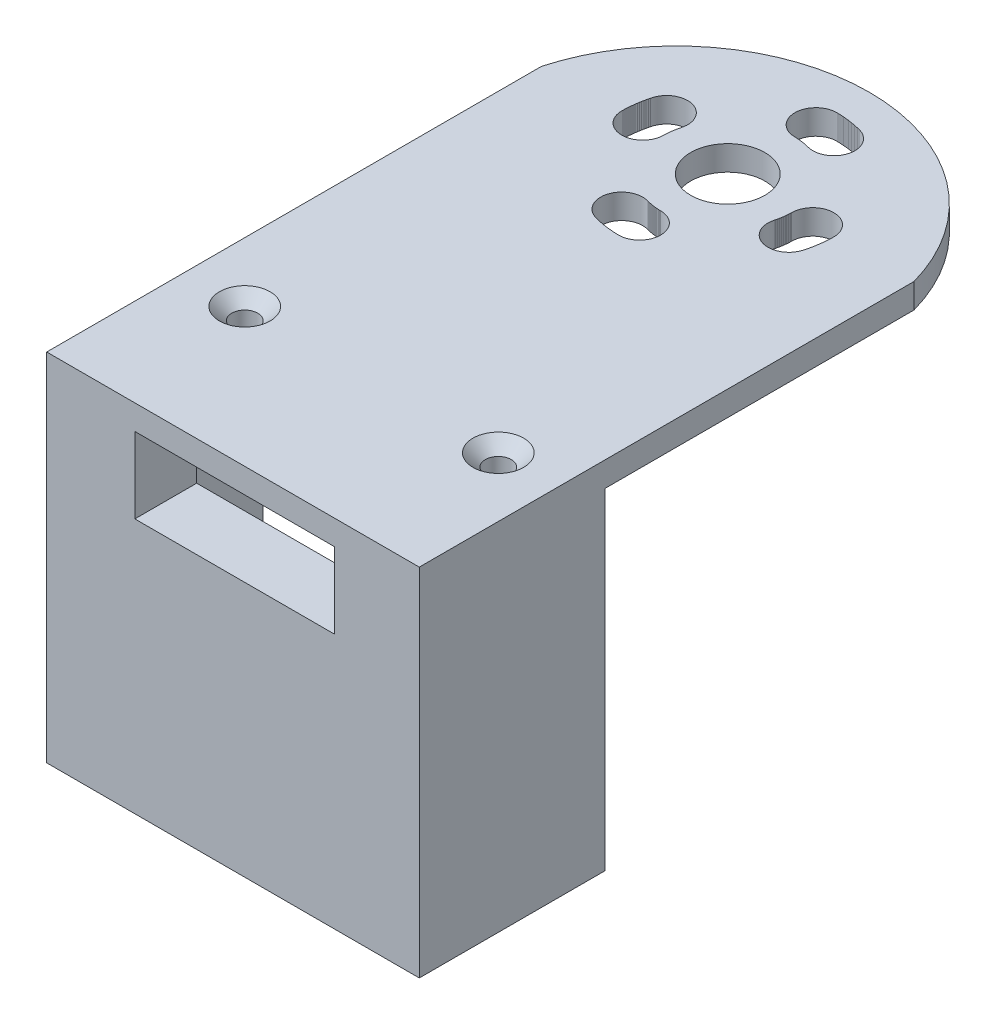
SolidWorks part; units mm, degrees
ref_plane "Front Plane" through (0, 0, 0) normal (0, 0, 1) x (1, 0, 0)
ref_plane "Top Plane" through (0, 0, 0) normal (0, 1, 0) x (1, 0, 0)
ref_plane "Right Plane" through (0, 0, 0) normal (1, 0, 0) x (0, 0, -1)
sketch "Sketch2" plane through (0, 0, 0) normal (0, 1, 0) x (1, 0, 0)
  line L0 (15.061, 0) -> (15.061, 32)
  line L1 (-12.561, 2.5) -> (12.561, 2.5)
  line L2 (-12.561, 2.5) -> (-12.561, 32)
  line L4 (12.561, 2.5) -> (12.561, 32)
  line L5 (15.061, 32) -> (12.561, 32)
  line L7 (-15.061, 32) -> (-15.061, 0)
  line L8 (-15.061, 0) -> (15.061, 0)
  line L10 (-15.061, 32) -> (-12.561, 32)
  point P4 (0, 2.5)
  point P12 (0, 0)
  dimension "D1" = 2.5
  dimension "D2" = 2.5
  dimension "D3" = 29.5
  dimension "D4" = 25.122
extrude "Boss-Extrude1" add sketch "Sketch2" along normal blind 32.5
sketch "Sketch4" plane through (0, 0, 0) normal (0, -1, 0) x (1, 0, 0)
  line L10 (-7.561, -6) -> (-7.561, 0)
  line L13 (-12.561, -2.5) -> (-12.561, -32) construction
  line L18 (-12.561, -10) -> (-7.561, -6)
  line L23 (12.561, -32) -> (12.561, -2.5) construction
  line L26 (12.561, -10) -> (7.561, -6)
  line L33 (-15.061, -32) -> (-15.061, 0) construction
  line L36 (15.061, 0) -> (15.061, -32) construction
  line L38 (-7.561, 0) -> (-15.061, 0)
  line L39 (7.561, -6) -> (7.561, 0)
  line L40 (7.561, 0) -> (15.061, 0)
  line L41 (-15.061, 0) -> (-15.061, -32)
  line L42 (-15.061, -32) -> (-12.561, -32)
  line L43 (-12.561, -32) -> (-15.061, -32) construction
  line L44 (-12.561, -32) -> (-12.561, -10)
  line L45 (12.561, -10) -> (12.561, -32)
  line L46 (12.561, -32) -> (15.061, -32)
  line L47 (15.061, -32) -> (15.061, 0)
  circle A2 centre (-10.2499, -4.95) radius 1.05
  circle A5 centre (10.2499, -4.95) radius 1.05
  dimension "D4" = 6
  dimension "D5" = 2.1
  dimension "D1" = 7.5
  dimension "D2" = 7.5
  dimension "D3" = 10
extrude "Boss-Extrude2" add sketch "Sketch4" along normal blind 2.5
sketch "Sketch5" plane through (0, 32.5, 0) normal (0, 1, 0) x (1, 0, 0)
  line L0 (-15.061, 32) -> (-10.2499, 32)
  line L9 (-10.2499, 32) -> (-6.25, 26)
  line L13 (-15.061, 0) -> (15.061, 0) construction
  line L14 (15.061, 0) -> (-15.061, 0)
  line L15 (-15.061, 0) -> (-15.061, 32)
  line L20 (15.061, 0) -> (15.061, 32)
  line L21 (-6.25, 26) -> (6.25, 26)
  line L22 (6.25, 26) -> (10.2499, 32)
  line L23 (10.2499, 32) -> (15.061, 32)
  circle A0 centre (-10.2499, 4.95) radius 1.05 construction
  circle A1 centre (-10.2499, 8.7) radius 1.05
  circle A2 centre (10.2499, 8.7) radius 1.05
  point P6 (0, 26)
  dimension "D4" = 0
  dimension "D1" = 8.7
  dimension "D2" = 12.5
  dimension "D3" = 20.4998
  dimension "D5" = 6
extrude "Boss-Extrude3" add sketch "Sketch5" along normal blind 3
sketch "Sketch6" plane through (-15.061, 0, 0) normal (-1, 0, 0) x (0, 0, 1)
  line L1 (-32, -2.5) -> (-32, 29.6998)
  line L5 (-32, 35.5) -> (-32, -2.5) construction
  line L7 (0, 35.5) -> (0, -2.5) construction
  line L8 (-12.5, -2.5) -> (-12.5, 35.5)
  line L9 (-32, 35.5) -> (0, 35.5) construction
  line L10 (-12.5, 35.5) -> (-32, 35.5)
  line L11 (-32, 35.5) -> (-32, 29.6998)
  line L12 (0, -2.5) -> (-32, -2.5) construction
  line L13 (-32, -2.5) -> (-12.5, -2.5)
  dimension "D2" = 12.5
extrude "Cut-Extrude1" cut sketch "Sketch6" against normal through all
ref_plane "Plane1" through (0, 16.5, 0) normal (0, -1, 0) x (-1, 0, 0)
sketch "Sketch13" plane through (0, 0, 0) normal (0, 0, 1) x (1, 0, 0)
  line L1 (-15.061, 35.5) -> (15.061, 35.5)
  line L2 (-15.061, 35.5) -> (-15.061, -2.5)
  line L3 (-15.061, -2.5) -> (15.061, -2.5)
  line L4 (15.061, 35.5) -> (15.061, -2.5)
extrude "Boss-Extrude7" add sketch "Sketch13" along normal blind 2.5
sketch "Sketch14" plane through (0, 0, 2.5) normal (0, 0, 1) x (1, 0, 0)
  line L0 (15.061, 35.5) -> (-15.061, 35.5) construction
  line L1 (-7.9361, 35.5) -> (8.206, 35.5)
  line L2 (-7.9361, 35.5) -> (-7.9361, 29.3758)
  line L3 (-7.9361, 29.3758) -> (8.206, 29.3758)
  line L4 (8.206, 35.5) -> (8.206, 29.3758)
extrude "Cut-Extrude2" cut sketch "Sketch14" against normal through all both and the other way through all
sketch "Sketch15" plane through (0, 0, -12.5) normal (0, 0, -1) x (-1, 0, 0)
  line L0 (15.061, -2.5) -> (15.061, 35.5) construction
  line L1 (-15.061, 35.5) -> (15.061, 35.5)
  line L2 (-15.061, 35.5) -> (-15.061, 37.5)
  line L3 (-15.061, 37.5) -> (15.061, 37.5)
  line L4 (15.061, 35.5) -> (15.061, 37.5)
  dimension "D1" = 2
extrude "Boss-Extrude8" add sketch "Sketch15" against normal up to surface (15 mm away) and the other way blind 40 up to face at (0.0675, 24.469, 2.5)
sketch "Sketch16" plane through (0, 37.5, 0) normal (0, 1, 0) x (1, 0, 0)
  line L0 (-15.061, -2.5) -> (15.061, -2.5) construction
  circle A0 centre (0, 37.5) radius 3
  dimension "D1" = 6
  dimension "D2" = 40
extrude "Cut-Extrude3" cut sketch "Sketch16" against normal through all both and the other way through all
sketch "Sketch17" plane through (0, 37.5, 0) normal (0, 1, 0) x (1, 0, 0)
  circle A0 centre (1.8162, 44.2603) radius 1.7
  circle A2 centre (0, 37.5) radius 3 construction
  dimension "D1" = 3.4
  dimension "D2" = 1.8162
  dimension "D3" = 6.7603
extrude "Cut-Extrude4" cut sketch "Sketch17" against normal through all both and the other way through all
ref_axis "Axis1" through (0, 35.5, -37.5) along (0, 1, 0)
pattern_circular "CirPattern1" count 15 every 1 about axis through (0, 35.5, -37.5) along (0, 1, 0) of "Cut-Extrude4"
pattern_circular "CirPattern2" count 4 over 360 about axis through (0, 35.5, -37.5) along (0, 1, 0) of "CirPattern1"
sketch "Sketch19" plane through (0, 0, -12.5) normal (0, 0, -1) x (-1, 0, 0)
  line L1 (-15.061, 8.7299) -> (15.061, 8.7299)
  line L2 (-15.061, 8.7299) -> (-15.061, -7.1783)
  line L3 (-15.061, -7.1783) -> (15.061, -7.1783)
  line L4 (15.061, 8.7299) -> (15.061, -7.1783)
extrude "Cut-Extrude5" cut sketch "Sketch19" against normal through all both and the other way through all
sketch "Sketch23" plane through (0, 37.5, 0) normal (0, 1, 0) x (1, 0, 0)
  line L9 (-15.061, 52.5) -> (-15.061, -2.5) construction
  line L10 (15.061, 52.5) -> (15.061, -2.5) construction
  line L11 (-15.061, 37.5) -> (-15.061, 55.7627)
  line L12 (-15.061, 55.7627) -> (15.061, 55.1353)
  line L13 (15.061, 55.1353) -> (15.061, 37.5)
  arc A1 (-15.061, 37.5) -> (15.061, 37.5) centre (0, 33.3084) cw
extrude "Cut-Extrude8" cut sketch "Sketch23" against normal through all both and the other way through all
sketch "Sketch24" plane through (0, 32.5, 0) normal (0, -1, 0) x (1, 0, 0)
  circle A0 centre (-10.2499, -8.7) radius 1.05
  circle A1 centre (10.2499, -8.7) radius 1.05
extrude "Cut-Extrude9" cut sketch "Sketch24" against normal through all
chamfer "Chamfer1" distance 1 angle 45 2 edges at (-10.2499, 37.5, -9.75) (10.2499, 37.5, -9.75)
